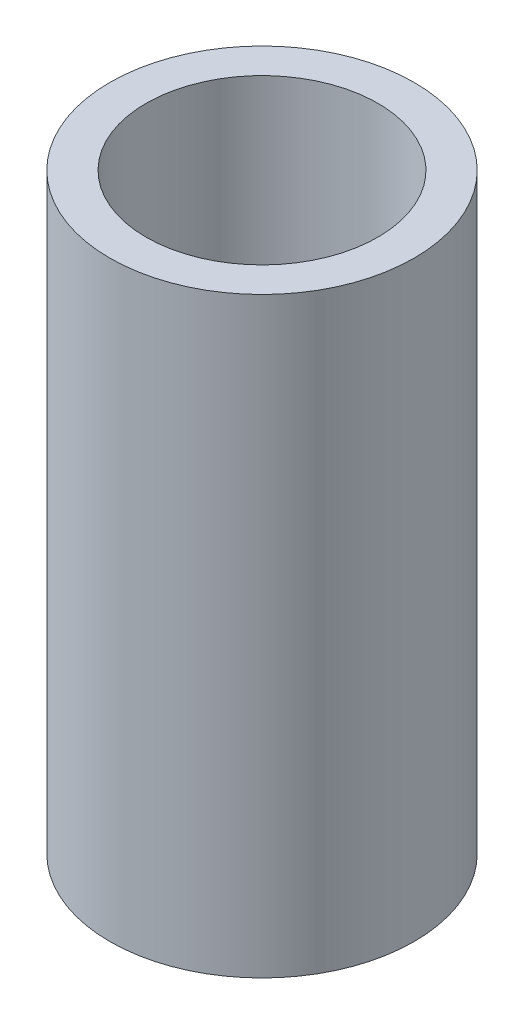
SolidWorks part; units mm, degrees
ref_plane "Front Plane" through (0, 0, 0) normal (0, 0, 1) x (1, 0, 0)
ref_plane "Top Plane" through (0, 0, 0) normal (0, 1, 0) x (1, 0, 0)
ref_plane "Right Plane" through (0, 0, 0) normal (1, 0, 0) x (0, 0, -1)
sketch "Sketch1" plane through (0, 0, 0) normal (0, 1, 0) x (1, 0, 0)
  circle A0 centre (0, 0) radius 40
  dimension "SLEEVE_OD" = 80
extrude "Boss-Extrude1" add sketch "Sketch1" along normal blind 155.5878
sketch "Sketch2" plane through (0, 0, 0) normal (0, 1, 0) x (1, 0, 0)
  circle A0 centre (0, 0) radius 30.4806
  dimension "BORE_D" = 60.9612
extrude "Cut-Extrude1" cut sketch "Sketch2" along normal through all
chamfer "Chamfer1" distance 3.6093 angle 61.93 rebuild error yes
